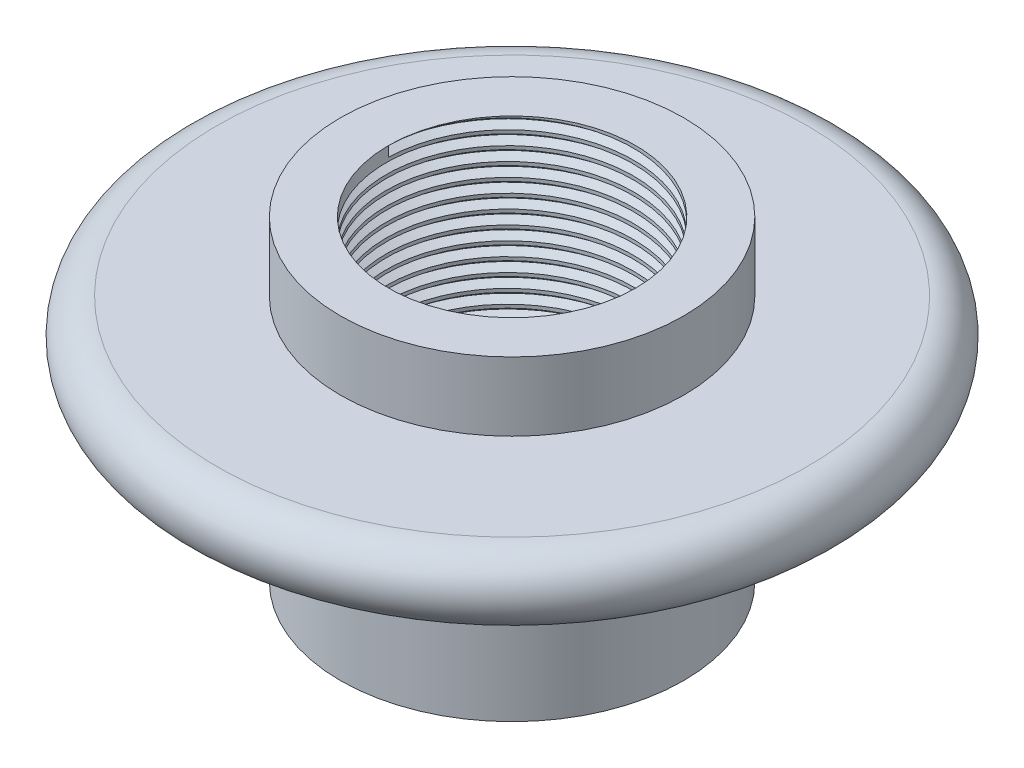
SolidWorks part; units mm, degrees
ref_plane "Front Plane" through (0, 0, 0) normal (0, 0, 1) x (1, 0, 0)
ref_plane "Top Plane" through (0, 0, 0) normal (0, 1, 0) x (1, 0, 0)
ref_plane "Right Plane" through (0, 0, 0) normal (1, 0, 0) x (0, 0, -1)
sketch "Sketch1" plane through (0, 0, 0) normal (0, 0, 1) x (1, 0, 0)
  line L0 (0, 0) -> (0, 49.4872) construction
  line L1 (18, 46) -> (18, 0)
  line L2 (18, 0) -> (25, 0)
  line L3 (25, 0) -> (25, 26)
  line L4 (25, 26) -> (43, 26)
  line L5 (18, 46) -> (25, 46)
  line L6 (25, 46) -> (25, 36)
  line L7 (25, 36) -> (43, 36)
  line L8 (43, 26) -> (43, 36) construction
  arc A0 (43, 26) -> (43, 36) centre (43, 31) ccw
  point P12 (14.8884, 0)
  dimension "D1" = 5
  dimension "D2" = 18
  dimension "D3" = 50
  dimension "D4" = 86
  dimension "D5" = 10
  dimension "D6" = 26
revolve "Revolve1" add sketch "Sketch1" angle 360 about L0
thread "Thread1" pitch 2 method cut profile "Thread Profile1" start angle 0, offset 0, length 0, pitch 2, diameter 36
ref_plane "Plane1" through (-18, 46, 0) normal (0, 0, 1) x (-1, 0, 0)
sketch "Thread Profile1" plane through (-18, 46, 0) normal (0, 0, 1) x (-1, 0, 0)
  line L0 (0, 0) -> (0, 2) construction
  line L1 (0, 0) -> (1.0825, 0.625)
  line L2 (1.0825, 0.625) -> (1.0825, 0.875)
  line L3 (1.0825, 0.875) -> (0, 1.5)
  line L4 (1.0825, 0.75) -> (0, 0.75) construction
  line L11 (0, 0) -> (0, 1.5)
  point P2 (0, 0)
  dimension "Pitch" = 2
  dimension "Profile_Angle" = 60
  dimension "Profile_Land" = 0.25
  dimension "Profile_Height" = 1.0825
